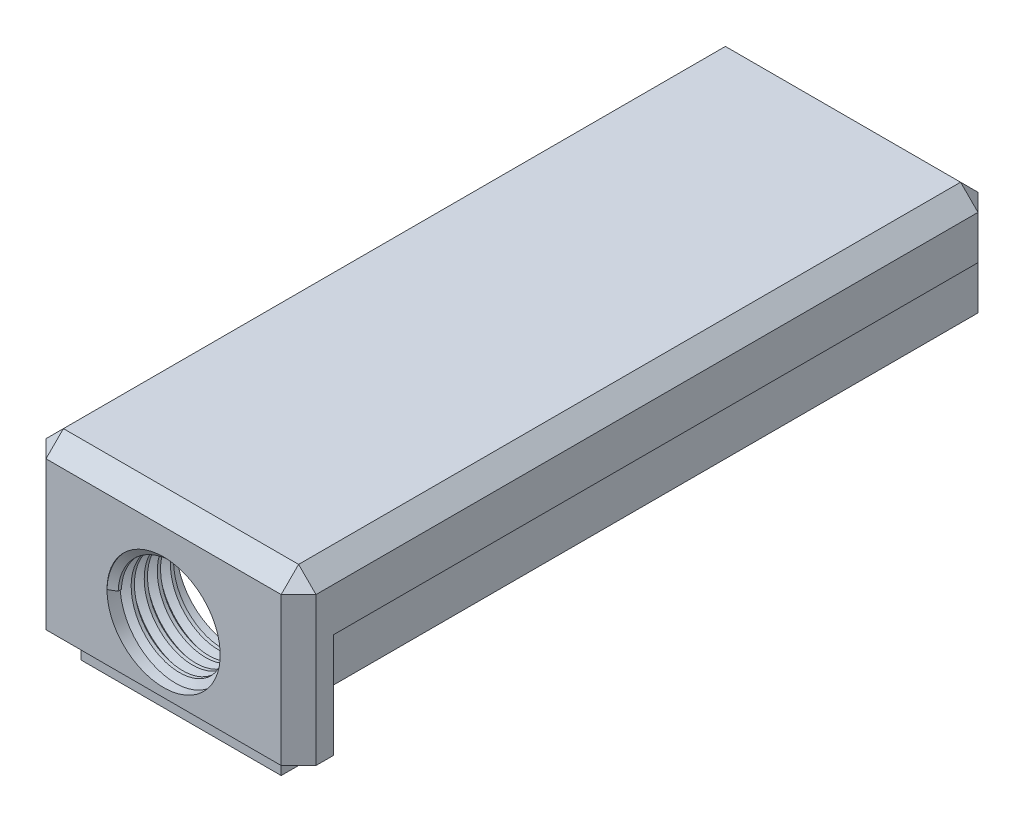
SolidWorks part; units mm, degrees
ref_plane "Front Plane" through (0, 0, 0) normal (0, 0, 1) x (1, 0, 0)
ref_plane "Top Plane" through (0, 0, 0) normal (0, 1, 0) x (1, 0, 0)
ref_plane "Right Plane" through (0, 0, 0) normal (1, 0, 0) x (0, 0, -1)
sketch "Sketch2" plane through (0, 0, 0) normal (0, 1, 0) x (1, 0, 0)
  line L9 (-3.5677, 279.1333) -> (27.4323, 279.1333)
  line L10 (-3.5677, 279.1333) -> (-3.5677, 359.1333)
  line L11 (-3.5677, 359.1333) -> (27.4323, 359.1333)
  line L12 (27.4323, 279.1333) -> (27.4323, 359.1333)
  dimension "D1" = 80
extrude "Boss-Extrude1" add sketch "Sketch2" along normal blind 7
sketch "Sketch3" plane through (0, 0, 0) normal (0, -1, 0) x (1, 0, 0)
  line L0 (27.4323, -359.1333) -> (-3.5677, -359.1333) construction
  line L1 (0.4323, -283.1333) -> (23.4323, -283.1333)
  line L2 (0.4323, -283.1333) -> (0.4323, -321.1333)
  line L3 (0.4323, -359.1333) -> (23.4323, -359.1333)
  line L4 (23.4323, -283.1333) -> (23.4323, -321.1333)
  line L8 (0.4323, -325.1333) -> (0.4323, -359.1333)
  line L9 (23.4323, -325.1333) -> (23.4323, -359.1333)
  arc A0 (23.4323, -321.1333) -> (23.4323, -325.1333) centre (23.4323, -323.1333) ccw
  arc A1 (0.4323, -325.1333) -> (0.4323, -321.1333) centre (0.4323, -323.1333) ccw
extrude "Boss-Extrude4" add sketch "Sketch3" against normal blind 3
sketch "Sketch6" plane through (0, 0, 0) normal (0, -1, 0) x (1, 0, 0)
  line L0 (27.4323, -359.1333) -> (-3.5677, -359.1333) construction
  line L1 (0.2323, -359.1333) -> (23.6323, -359.1333)
  line L2 (0.2323, -359.1333) -> (0.2323, -354.8333)
  line L3 (0.2323, -283.1333) -> (23.6323, -283.1333)
  line L4 (23.6323, -359.1333) -> (23.6323, -354.8333)
  line L5 (-3.5677, -279.1333) -> (27.4323, -279.1333) construction
  line L6 (-3.5677, -359.1333) -> (-3.5677, -279.1333) construction
  line L7 (27.4323, -279.1333) -> (27.4323, -359.1333) construction
  line L8 (0.2323, -351.4333) -> (0.2323, -313.1333)
  line L9 (23.6323, -351.4333) -> (23.6323, -313.1333)
  line L10 (23.6323, -301.1333) -> (23.1323, -301.1333)
  line L11 (23.1323, -301.1333) -> (23.1323, -313.1333)
  line L12 (23.1323, -313.1333) -> (23.6323, -313.1333)
  line L13 (23.6323, -301.1333) -> (23.6323, -283.1333)
  line L14 (0.2323, -301.1333) -> (0.7323, -301.1333)
  line L15 (0.7323, -301.1333) -> (0.7323, -313.1333)
  line L16 (0.7323, -313.1333) -> (0.2323, -313.1333)
  line L17 (0.2323, -301.1333) -> (0.2323, -283.1333)
  arc A0 (0.2323, -354.8333) -> (0.2323, -351.4333) centre (0.2323, -353.1333) ccw
  arc A1 (23.6323, -351.4333) -> (23.6323, -354.8333) centre (23.6323, -353.1333) ccw
  dimension "D4" = 6
  dimension "D5" = 18
  dimension "D9" = 0.5
  dimension "D1" = 4
  dimension "D2" = 3.8
  dimension "D3" = 3.8
  dimension "D6" = 12
  dimension "D7" = 0.5
  dimension "D8" = 12
extrude "Cut-Extrude1" cut sketch "Sketch6" against normal blind 3
sketch "Sketch10" plane through (0, 3, 0) normal (0, -1, 0) x (1, 0, 0)
  line L0 (8.2323, -337.1333) -> (15.2323, -337.1333) construction
  line L1 (8.2323, -335.6333) -> (15.2323, -335.6333)
  line L2 (8.2323, -338.6333) -> (15.2323, -338.6333)
  line L3 (0.2323, -359.1333) -> (23.6323, -359.1333) construction
  line L4 (0.2323, -313.1333) -> (0.2323, -351.4333) construction
  arc A0 (8.2323, -335.6333) -> (8.2323, -338.6333) centre (8.2323, -337.1333) ccw
  arc A1 (15.2323, -338.6333) -> (15.2323, -335.6333) centre (15.2323, -337.1333) ccw
  point P2 (11.7323, -337.1333)
  dimension "D1" = 7
  dimension "D2" = 3
  dimension "D3" = 22
  dimension "D4" = 11.5
extrude "Cut-Extrude2" cut sketch "Sketch10" against normal blind 3
sketch "Sketch11" plane through (0, 3, 0) normal (0, -1, 0) x (1, 0, 0)
  line L17 (23.6323, -283.1333) -> (0.2323, -283.1333) construction
  circle A0 centre (8.2623, -307.1333) radius 1.3
  circle A1 centre (15.5352, -307.1333) radius 1.3
  dimension "D1" = 24
extrude "Boss-Extrude6" add sketch "Sketch11" along normal blind 5
sketch "Sketch12" plane through (0, 0, 0) normal (0, -1, 0) x (1, 0, 0)
  line L0 (27.4323, -279.1333) -> (27.4323, -359.1333) construction
  line L1 (-3.5677, -279.1333) -> (27.4323, -279.1333)
  line L2 (-3.5677, -279.1333) -> (-3.5677, -283.1333)
  line L3 (-3.5677, -283.1333) -> (27.4323, -283.1333)
  line L4 (27.4323, -279.1333) -> (27.4323, -283.1333)
  dimension "D1" = 4
extrude "Boss-Extrude7" add sketch "Sketch12" along normal blind 12
sketch "Sketch13" plane through (0, 0, 0) normal (0, -1, 0) x (1, 0, 0)
  line L0 (-3.5677, -283.1333) -> (0.2323, -283.1333) construction
  line L1 (-2.5677, -283.1333) -> (-0.5677, -283.1333)
  line L2 (-2.5677, -283.1333) -> (-2.5677, -358.1333)
  line L3 (-2.5677, -358.1333) -> (-0.5677, -358.1333)
  line L4 (-0.5677, -283.1333) -> (-0.5677, -356.1333)
  line L5 (-3.5677, -359.1333) -> (-3.5677, -283.1333) construction
  line L6 (0.2323, -359.1333) -> (-3.5677, -359.1333) construction
  line L7 (0.2323, -354.8333) -> (0.2323, -359.1333) construction
  line L8 (-0.5677, -358.1333) -> (0.2323, -358.1333)
  line L10 (-0.5677, -356.1333) -> (0.2323, -356.1333)
  line L11 (0.2323, -358.1333) -> (0.2323, -356.1333)
  dimension "D1" = 2
  dimension "D2" = 1
  dimension "D3" = 1
  dimension "D4" = 2
extrude "Boss-Extrude8" add sketch "Sketch13" along normal blind 6 contours L1 L4 L10 L11 L8 L3 L2
sketch "Sketch14" plane through (0, 0, 0) normal (0, -1, 0) x (1, 0, 0)
  line L0 (23.6323, -283.1333) -> (27.4323, -283.1333) construction
  line L1 (24.4323, -283.1333) -> (26.4323, -283.1333)
  line L2 (24.4323, -283.1333) -> (24.4323, -356.1333)
  line L3 (24.4323, -358.1333) -> (26.4323, -358.1333)
  line L4 (26.4323, -283.1333) -> (26.4323, -358.1333)
  line L5 (27.4323, -283.1333) -> (27.4323, -359.1333) construction
  line L6 (27.4323, -359.1333) -> (23.6323, -359.1333) construction
  line L9 (23.6323, -359.1333) -> (23.6323, -354.8333) construction
  line L10 (24.4323, -358.1333) -> (23.6323, -358.1333)
  line L12 (24.4323, -356.1333) -> (23.6323, -356.1333)
  line L13 (23.6323, -358.1333) -> (23.6323, -356.1333)
  dimension "D1" = 2
  dimension "D2" = 1
  dimension "D3" = 1
  dimension "D4" = 2
extrude "Boss-Extrude9" add sketch "Sketch14" along normal blind 6 contours L1 L4 L3 L10 L13 L12 L2
chamfer "Chamfer2" distance 2 angle 45 8 edges at (-3.5677, 3.5, -359.1333) (-3.5677, -2.5, -279.1333) (-3.5677, 7, -319.1333) (11.9323, 7, -279.1333) (27.4323, -2.5, -279.1333) (11.9323, 7, -359.1333) (27.4323, 3.5, -359.1333) (27.4323, 7, -319.1333)
sketch "Sketch15" plane through (0, -12, 0) normal (0, -1, 0) x (1, 0, 0)
  line L0 (-3.5677, -283.1333) -> (27.4323, -283.1333) construction
  line L1 (0.4323, -281.1333) -> (23.4323, -281.1333)
  line L2 (0.4323, -281.1333) -> (0.4323, -283.1333)
  line L3 (0.4323, -283.1333) -> (23.4323, -283.1333)
  line L4 (23.4323, -281.1333) -> (23.4323, -283.1333)
  line L5 (-3.5677, -281.1333) -> (-3.5677, -283.1333) construction
  line L6 (27.4323, -283.1333) -> (27.4323, -281.1333) construction
  dimension "D1" = 4
  dimension "D2" = 4
  dimension "D3" = 2
extrude "Boss-Extrude10" add sketch "Sketch15" along normal blind 3 contours L2 L1 L4 L3
sketch "Sketch16" plane through (0, 0, -283.1333) normal (0, 0, -1) x (-1, 0, 0)
  line L0 (-23.4323, -12) -> (-27.4323, -12) construction
  line L1 (3.5677, -12) -> (3.5677, 0) construction
  circle A0 centre (-11.9323, -4.5) radius 7.45
  dimension "D1" = 7.5
  dimension "D2" = 15.5
extrude "Boss-Extrude15" add sketch "Sketch16" along normal blind 4
hole_wizard "M12 Clearance Hole1" positions "Sketch17" profile "Sketch19" hole size "M12" standard "DIN"
sketch "Sketch17" plane through (0, 0, -279.1333) normal (0, 0, 1) x (1, 0, 0)
  line L0 (25.4323, -12) -> (-1.5677, -12) construction
  line L1 (27.4323, 5) -> (27.4323, -12) construction
  point P0 (11.9323, -4.5)
  dimension "D1" = 7.5
  dimension "D2" = 15.5
sketch "Sketch19" plane through (11.9323, -4.5, -279.1333) normal (1, 0, 0) x (0, -1, 0)
  line L0 (0, 0) -> (0, 11.9056)
  line L1 (0, 11.9056) -> (6.5, 8)
  line L2 (6.5, 8) -> (6.5, 0)
  line L5 (6.5, 0) -> (0, 0)
  line L10 (0, 11.9056) -> (-6.5, 8) construction
  line L11 (0, -6.35) -> (0, 107.95) construction
  dimension "Hole Dia." = 13
  dimension "Hole Depth" = 8
  dimension "Drill Angle" = 118
thread "Thread1" pitch 1.5 method extrude profile "Thread Profile1" start angle 0, offset 0, length 0, pitch 1.5, diameter 13
ref_plane "Plane1" through (5.4323, -4.5, -279.1333) normal (0, -1, 0) x (-1, 0, 0)
sketch "Thread Profile1" plane through (5.4323, -4.5, -279.1333) normal (0, -1, 0) x (-1, 0, 0)
  line L0 (0, 0) -> (0, 1.5) construction
  line L11 (0, 0) -> (0, 1.3125)
  line L12 (0, 1.3125) -> (-0.8119, 0.8437)
  line L13 (-0.8119, 0.8437) -> (-0.8119, 0.4687)
  line L15 (-0.8119, 0.4687) -> (0, 0)
  line L17 (-0.8119, 0.6562) -> (0, 0.6562) construction
  point P2 (0, 0)
  dimension "Pitch" = 1.5
  dimension "Profile_Angle" = 60
  dimension "Profile_Land" = 0.375
  dimension "Profile_Height" = 0.8119
